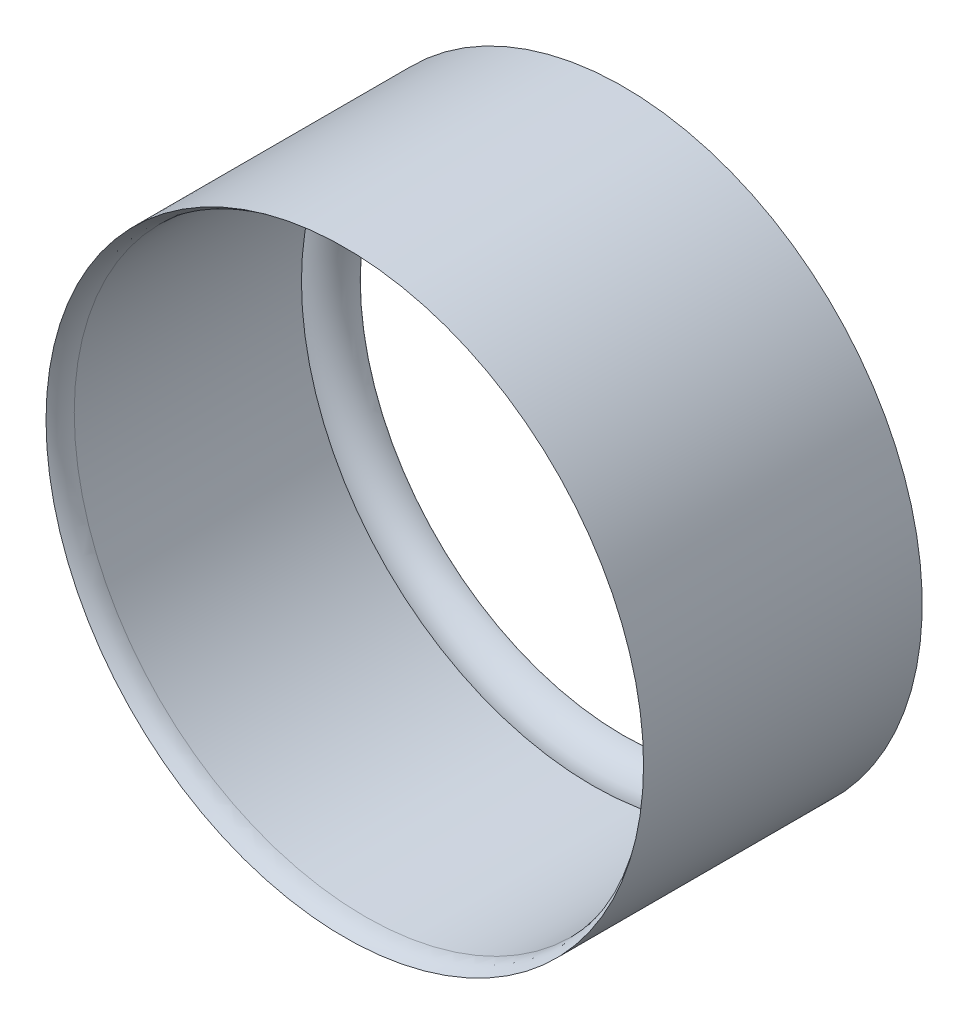
SolidWorks part; units mm, degrees
ref_plane "Alzado" through (0, 0, 0) normal (1, 0, 0) x (0, 1, 0)
ref_plane "Planta" through (0, 0, 0) normal (0, 0, 1) x (0, 1, 0)
ref_plane "Vista lateral" through (0, 0, 0) normal (0, 1, 0) x (-1, 0, 0)
sketch "Croquis1" plane through (0, 0, 0) normal (0, 0, 1) x (0, 1, 0)
  circle A0 centre (0, 0) radius 470
  circle A1 centre (0, 0) radius 482.5
  dimension "D1" = 940
  dimension "D2" = 965
extrude "Saliente-Extruir1" add sketch "Croquis1" along normal blind 400
fillet "Redondeo1" radius 50 1 edges at (470, 0, 400)
sketch "Croquis2" plane through (0, 0, 0) normal (0, 0, -1) x (1, 0, 0)
  circle A0 centre (0, 0) radius 482.5
  circle A1 centre (0, 0) radius 425
  dimension "D1" = 850
extrude "Saliente-Extruir2" add sketch "Croquis2" along normal blind 50
fillet "Redondeo3" radius 50 1 edges at (-425, 0, 0)
